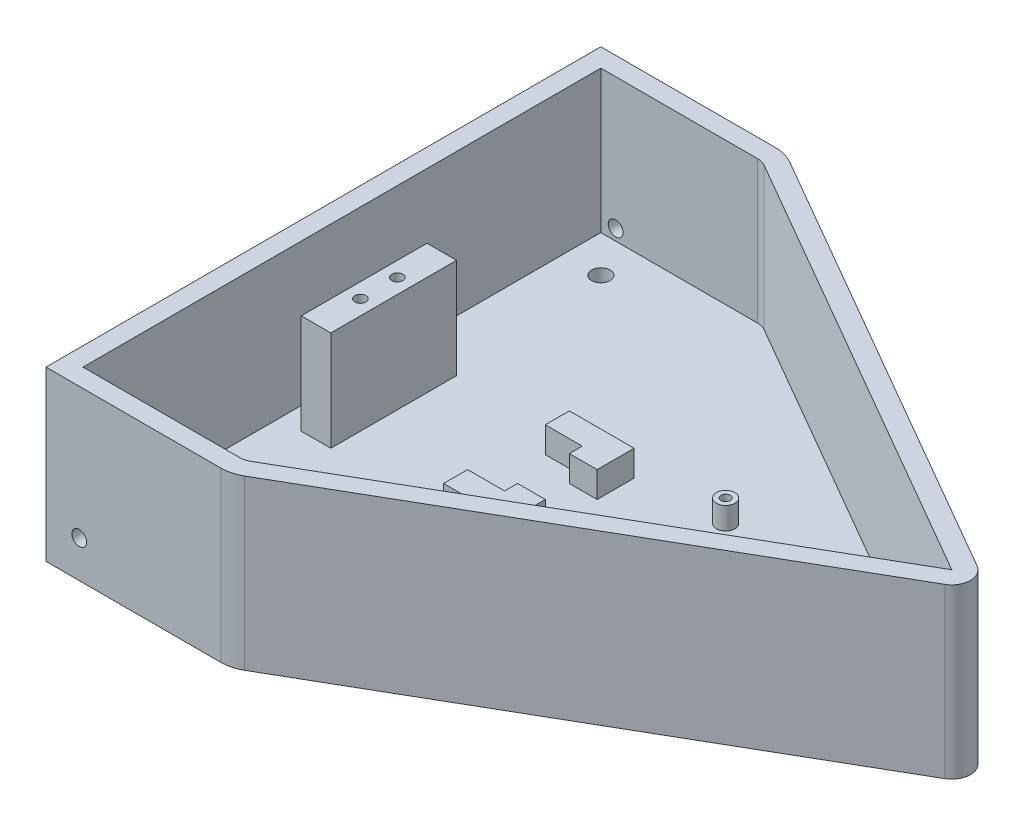
SolidWorks part; units mm, degrees
note: The reader was unsure of these and kept them because the rebuilt part matched: shared geometry of "Sketch7<4>", "Sketch7<5>".
ref_plane "Alzado" through (0, 0, 0) normal (0, 0, 1) x (1, 0, 0)
ref_plane "Planta" through (0, 0, 0) normal (0, 1, 0) x (1, 0, 0)
ref_plane "Vista lateral" through (0, 0, 0) normal (1, 0, 0) x (0, 0, -1)
sketch "Sketch1" plane through (0, 0, 0) normal (0, 1, 0) x (1, 0, 0)
  line L1 (75.0555, 0) -> (-54.8483, 75)
  line L3 (-54.8483, -75) -> (75.0555, 0)
  line L4 (-54.8483, 75) -> (-104.8483, 75)
  line L6 (-54.8483, -75) -> (-104.8483, -75)
  line L7 (-104.8483, 75) -> (-104.8483, -75)
  line L8 (-37.5278, 65) -> (-37.5278, -65) [skipped]
  circle A0 centre (0, 0) radius 37.5278 construction
  dimension "D3" = 75.0555
  dimension "D1" = 150
  dimension "D2" = 50
  dimension "D4" = 50
  dimension "D5" = 150
extrude "Boss-Extrude1" add sketch "Sketch1" along normal blind 7
fillet "Fillet1" radius 5 1 edges at (75.0555, 3.5, 0)
fillet "Fillet2" radius 10 2 edges at (-54.8483, 3.5, -75) (-54.8483, 3.5, 75)
sketch "Sketch3" plane through (0, 7, 0) normal (0, 1, 0) x (1, 0, 0)
  line L0 (-57.5278, 75) -> (-104.8483, 75) construction
  line L1 (-104.8483, 75) -> (-104.8483, -75) construction
  line L2 (-104.8483, -75) -> (-57.5278, -75) construction
  circle A0 centre (-89.8483, 60) radius 2.5
  circle A1 centre (-89.8483, -60) radius 2.5
  dimension "D3" = 5
  dimension "D1" = 15
  dimension "D2" = 15
  dimension "D4" = 15
  dimension "D5" = 15
extrude "Cut-Extrude1" cut sketch "Sketch3" against normal up to next contours A0 | A1
sketch "Sketch6" plane through (0, 7, 0) normal (0, 1, 0) x (1, 0, 0)
  line L0 (-57.5278, 75) -> (-104.8483, 75) construction
  line L1 (-14.8483, 18.75) -> (-12.3483, 18.75)
  line L2 (-14.8483, 18.75) -> (-14.8483, 16.25)
  line L3 (-14.8483, -18.75) -> (-12.3483, -18.75)
  line L4 (22.6517, 18.75) -> (22.6517, 16.25)
  line L5 (20.1517, 18.75) -> (22.6517, 18.75)
  line L6 (-14.8483, -16.25) -> (-14.8483, -18.75)
  line L7 (-104.8483, 75) -> (-104.8483, -75) construction
  line L8 (20.1517, -18.75) -> (22.6517, -18.75)
  line L9 (22.6517, -16.25) -> (22.6517, -18.75)
  circle A0 centre (22.6517, 18.75) radius 1.25
  circle A1 centre (-14.8483, 18.75) radius 1.25
  circle A2 centre (-14.8483, -18.75) radius 1.25
  circle A3 centre (22.6517, -18.75) radius 1.25
  circle A4 centre (-14.8483, 18.75) radius 2.5
  circle A5 centre (22.6517, 18.75) radius 2.5
  circle A6 centre (22.6517, -18.75) radius 2.5
  circle A7 centre (-14.8483, -18.75) radius 2.5
  dimension "D5" = 2.5
  dimension "D6" = 2.5
  dimension "D7" = 2.5
  dimension "D8" = 2.5
  dimension "D9" = 5
  dimension "D10" = 5
  dimension "D11" = 5
  dimension "D12" = 5
  dimension "D1" = 37.5
  dimension "D2" = 37.5
  dimension "D3" = 56.25
  dimension "D4" = 90
extrude "Boss-Extrude2" add sketch "Sketch6" along normal blind 6 contours L1 A4 L2 A1 | L4 A5 L5 A0 | L8 A6 L9 A3 | L9 A6 L8 A3 | L6 A7 L3 A2 | L3 A7 L6 A2 | L2 A4 L1 A1 | L5 A5 L4 A0
sketch "Sketch7" plane through (0, 7, 0) normal (0, 1, 0) x (1, 0, 0)
  line L0 (-104.8483, -75) -> (-57.5278, -75) construction
  line L1 (-89.8483, 5) -> (-41.8483, 5)
  line L2 (-89.8483, 5) -> (-89.8483, -5)
  line L3 (-89.8483, -5) -> (-41.8483, -5)
  line L4 (-41.8483, 5) -> (-41.8483, -5)
  line L5 (-104.8483, 75) -> (-104.8483, -75) construction
  line L6 (-83.3483, -10.0065) -> (-48.3483, -10.0065) construction
  line L7 (-93.8483, 17) -> (-85.8483, 17)
  line L8 (-93.8483, 17) -> (-93.8483, -17)
  line L9 (-93.8483, -17) -> (-85.8483, -17)
  line L10 (-85.8483, 17) -> (-85.8483, -17)
  line L11 (-45.8483, 17) -> (-37.8483, 17)
  line L12 (-45.3483, 10.4935) -> (-45.3483, 7)
  line L13 (-45.8483, -17) -> (-37.8483, -17)
  line L14 (-37.8483, 17) -> (-37.8483, 7)
  line L15 (-45.8483, -17) -> (-55.3483, -17)
  line L17 (-45.3483, -10.5065) -> (-55.3483, -10.5065)
  line L18 (-55.3483, -17) -> (-55.3483, -10.5065)
  line L19 (-45.8483, 17) -> (-55.3483, 17)
  line L21 (-45.3483, 10.4935) -> (-55.3483, 10.4935)
  line L22 (-55.3483, 17) -> (-55.3483, 10.4935)
  line L23 (-48.3483, 9.9935) -> (-83.3483, 9.9935) construction
  line L24 (-45.3483, 7) -> (-37.8483, 7)
  line L25 (-45.3483, -7) -> (-37.8483, -7)
  line L26 (-45.3483, -7) -> (-45.3483, -10.5065)
  line L27 (-37.8483, -7) -> (-37.8483, -17)
  line L28 (-45.3483, 5) -> (-45.3483, -5)
  dimension "D1" = 10
  dimension "D2" = 48
  dimension "D3" = 70
  dimension "D4" = 15
  dimension "D5" = 12
  dimension "D6" = 12
  dimension "D7" = 4
  dimension "D8" = 4
  dimension "D9" = 12
  dimension "D10" = 4
  dimension "D11" = 3.5
  dimension "D12" = 12
  dimension "D13" = 0.5
  dimension "D14" = 10
  dimension "D15" = 0.5
  dimension "D16" = 10
  dimension "D17" = 10
  dimension "D18" = 10
extrude "Boss-Extrude3" add sketch "Sketch7" along normal up to vertex (27 mm away) contours L10 L7 L8 L9 L3 L2 L1 | L10 L1 L2 L3
sketch "Sketch8" plane through (0, 34, 0) normal (0, 1, 0) x (1, 0, 0)
  line L0 (-93.8483, 17) -> (-85.8483, 17) construction
  line L1 (-93.8483, 17) -> (-93.8483, -17) construction
  line L2 (-93.8483, -17) -> (-85.8483, -17) construction
  circle A0 centre (-89.8483, -5) radius 1.5
  circle A1 centre (-89.8483, 5) radius 1.5
  dimension "D5" = 3
  dimension "D6" = 3
  dimension "D1" = 12
  dimension "D2" = 4
  dimension "D3" = 12
  dimension "D4" = 4
extrude "Cut-Extrude2" cut sketch "Sketch8" against normal blind 10
extrude "Boss-Extrude4" add sketch "Sketch7<4>" along normal blind 7 contours L17 L18 L15 L13 L27 L25 L26
sketch "Sketch7<4>" plane through (0, 7, 0) normal (0, 1, 0) x (1, 0, 0) same geometry as "Sketch7"
extrude "Boss-Extrude5" add sketch "Sketch7<5>" along normal blind 7 contours L21 L22 L19 L11 L14 L24 L12
sketch "Sketch7<5>" plane through (0, 7, 0) normal (0, 1, 0) x (1, 0, 0) same geometry as "Sketch7"
ref_plane "Plane1" through (-104.8483, 7, 75) normal (0, 0, 1) x (1, 0, 0)
sketch "Sketch11" plane through (0, 7, 0) normal (0, 1, 0) x (1, 0, 0)
  line L10 (-99.8483, -70) -> (-57.5278, -70)
  line L11 (-55.0278, -69.3301) -> (65.0555, 0)
  line L12 (65.0555, 0) -> (-55.0278, 69.3301)
  line L13 (-57.5278, 70) -> (-99.8483, 70)
  line L14 (-99.8483, 70) -> (-99.8483, -70)
  line L15 (-99.8483, -70) -> (-57.5278, -70)
  line L16 (-55.0278, -69.3301) -> (65.0555, 0)
  line L17 (65.0555, 0) -> (-55.0278, 69.3301)
  line L18 (-57.5278, 70) -> (-99.8483, 70)
  line L19 (-99.8483, 70) -> (-99.8483, -70)
  arc A6 (-57.5278, -70) -> (-55.0278, -69.3301) centre (-57.5278, -65) ccw
  arc A7 (-55.0278, 69.3301) -> (-57.5278, 70) centre (-57.5278, 65) ccw
  arc A8 (-57.5278, -70) -> (-55.0278, -69.3301) centre (-57.5278, -65) ccw
  arc A9 (-55.0278, 69.3301) -> (-57.5278, 70) centre (-57.5278, 65) ccw
  circle M8 centre (22.6517, 18.75) radius 2.5
  circle M9 centre (-14.8483, 18.75) radius 2.5
  circle M10 centre (-14.8483, -18.75) radius 2.5
  circle M11 centre (22.6517, -18.75) radius 2.5
  circle M12 centre (-89.8483, 60) radius 2.5
  circle M13 centre (-89.8483, -60) radius 2.5
  line M14 (-104.8483, -75) -> (-57.5278, -75)
  arc M15 (-57.5278, -75) -> (-52.5278, -73.6603) centre (-57.5278, -65) ccw
  line M16 (-52.5278, -73.6603) -> (67.5555, -4.3301)
  arc M17 (67.5555, -4.3301) -> (67.5555, 4.3301) centre (65.0555, 0) ccw
  line M18 (67.5555, 4.3301) -> (-52.5278, 73.6603)
  arc M19 (-52.5278, 73.6603) -> (-57.5278, 75) centre (-57.5278, 65) ccw
  line M20 (-57.5278, 75) -> (-104.8483, 75)
  line M21 (-104.8483, 75) -> (-104.8483, -75)
  line M22 (-85.8483, 17) -> (-85.8483, -17)
  line M23 (-85.8483, -17) -> (-93.8483, -17)
  line M24 (-93.8483, -17) -> (-93.8483, 17)
  line M25 (-93.8483, 17) -> (-85.8483, 17)
  line M26 (-55.3483, -10.5065) -> (-45.3483, -10.5065)
  line M27 (-45.3483, -10.5065) -> (-45.3483, -7)
  line M28 (-45.3483, -7) -> (-37.8483, -7)
  line M29 (-37.8483, -7) -> (-37.8483, -17)
  line M30 (-37.8483, -17) -> (-55.3483, -17)
  line M31 (-55.3483, -17) -> (-55.3483, -10.5065)
  line M32 (-37.8483, 7) -> (-45.3483, 7)
  line M33 (-45.3483, 7) -> (-45.3483, 10.4935)
  line M34 (-45.3483, 10.4935) -> (-55.3483, 10.4935)
  line M35 (-55.3483, 10.4935) -> (-55.3483, 17)
  line M36 (-55.3483, 17) -> (-37.8483, 17)
  line M37 (-37.8483, 17) -> (-37.8483, 7)
  dimension "D1" = 5
extrude "Boss-Extrude6" add sketch "Sketch11" along normal up to surface (38.5 mm away) contours A9 L17 L16 A8 L15 L19 L18 M21 M14 M15 M16 M17 M18 M19 M20 | L17 A9 L18 L19 L15 A8 L16 M8 M10 M12 M37 M32 M33 M34 M35 M36 M31 M26 M27 M28 M29 M30 M25 M22 M23 M24 M13 M11 M9
sketch "Sketch14" plane through (0, 0, 75) normal (0, 0, 1) x (1, 0, 0)
  line L0 (-104.8483, 45.5) -> (-104.8483, 0) construction
  line L1 (-104.8483, 0) -> (-57.5278, 0) construction
  circle A0 centre (-95.8483, 10) radius 2
  dimension "D1" = 9
  dimension "D2" = 4
  dimension "D3" = 10
extrude "Cut-Extrude3" cut sketch "Sketch14" against normal blind 10
sketch "Sketch15" plane through (0, 0, -75) normal (0, 0, -1) x (-1, 0, 0)
  line L0 (104.8483, 45.5) -> (104.8483, 0) construction
  line L1 (57.5278, 0) -> (104.8483, 0) construction
  circle A0 centre (95.8483, 10) radius 2
  dimension "D1" = 4
  dimension "D3" = 10
  dimension "D2" = 9
extrude "Cut-Extrude4" cut sketch "Sketch15" against normal blind 10
